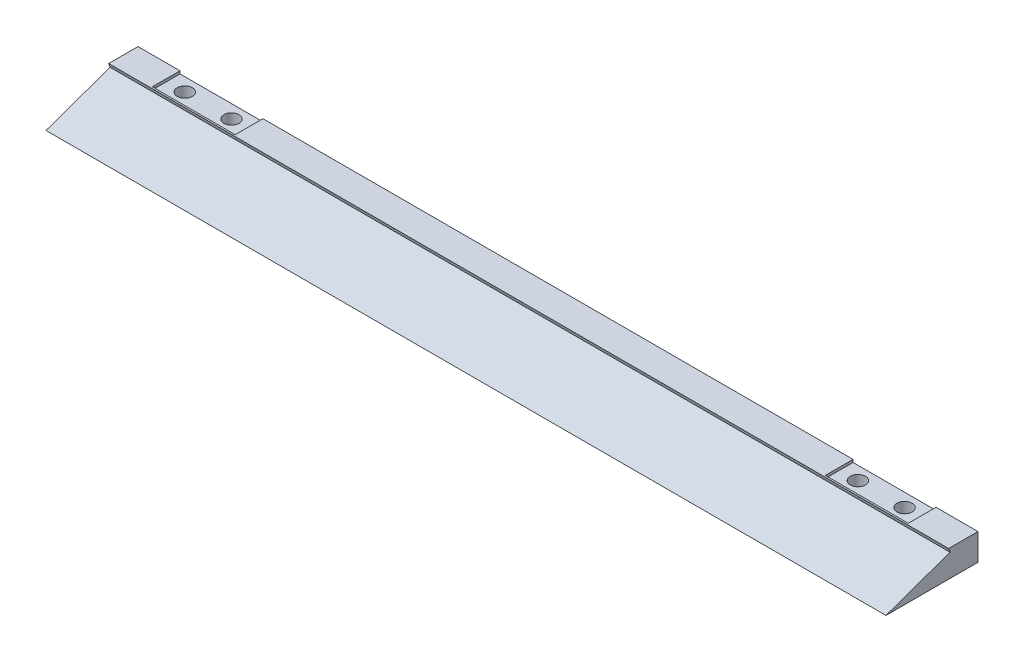
SolidWorks part; units mm, degrees
material "1023 Carbon Steel Sheet (SS)"
ref_plane "Front Plane" through (0, 0, 0) normal (0, 0, 1) x (1, 0, 0)
ref_plane "Top Plane" through (0, 0, 0) normal (0, 1, 0) x (1, 0, 0)
ref_plane "Right Plane" through (0, 0, 0) normal (1, 0, 0) x (0, 0, -1)
sketch "Sketch1" plane through (0, 0, 0) normal (0, 1, 0) x (1, 0, 0)
  line L1 (-100, -15) -> (100, -15)
  line L2 (-100, -15) -> (-100, 15)
  line L3 (-100, 15) -> (100, 15)
  line L4 (100, -15) -> (100, 15)
  line L5 (-100, -15) -> (100, 15) construction
  line L6 (-100, 15) -> (100, -15) construction
  point P0 (0, 0)
  dimension "D1" = 200
  dimension "D2" = 30
extrude "Base" add sketch "Sketch1" along normal blind 6.35
ref_plane "Midplane" through (0, 0, 0) normal (1, 0, 0) x (0, 0, -1)
sketch "Sketch2" plane through (100, 0, 0) normal (1, 0, 0) x (0, 0, -1)
  line L0 (-6.9075, 0) -> (11, 6.35)
  line L1 (-15, 0) -> (15, 0) construction
  line L2 (-15, 6.35) -> (15, 6.35) construction
  line L3 (11, 6.35) -> (11, 0)
  line L4 (11, 0) -> (-6.9075, 0)
  line L5 (15, 6.35) -> (15, 0) construction
  line L7 (11, 6.35) -> (-15, 6.35)
  line L8 (-15, 6.35) -> (-15, 0)
  line L9 (-15, 0) -> (-6.9075, 0)
  line L10 (8.3421, 5.4075) -> (8.0079, 6.35)
  line M3 (-15, 0) -> (15, 0)
  line M5 (15, 6.35) -> (-15, 6.35)
  line M6 (-15, 6.35) -> (-15, 0)
  dimension "D1" = 19
  dimension "D2" = 4
  dimension "D3" = 1
extrude "WedgeCut" cut sketch "Sketch2" against normal up to next contours L0 M3 M5 M6 region at (100, 3.7005, 5.8885)
sketch "Sketch3" plane through (0, 6.35, 0) normal (0, 1, 0) x (1, 0, 0)
  line L0 (-100, 15) -> (-100, 8.0079) construction
  line L1 (-90, 8.396) -> (-70.254, 8.396)
  line L2 (-90, 8.396) -> (-90, 15)
  line L3 (-90, 15) -> (-70.254, 15)
  line L4 (-70.254, 8.396) -> (-70.254, 15)
  line L5 (-90, 8.396) -> (-70.254, 15) construction
  line L6 (-90, 15) -> (-70.254, 8.396) construction
  line L7 (70.254, 15) -> (90, 15)
  line L8 (70.254, 15) -> (70.254, 8.396)
  line L9 (70.254, 8.396) -> (90, 8.396)
  line L10 (90, 15) -> (90, 8.396)
  line L11 (70.254, 15) -> (90, 8.396) construction
  line L12 (70.254, 8.396) -> (90, 15) construction
  line L13 (100, 15) -> (-100, 15) construction
  line L14 (100, 8.0079) -> (100, 15) construction
  point P0 (-80.127, 11.698)
  point P5 (80.127, 11.698)
  dimension "D1" = 6.604
  dimension "D2" = 19.746
  dimension "D3" = 10
  dimension "D4" = 19.746
  dimension "D5" = 10
  dimension "D6" = 6.604
extrude "Hinge Cutout" cut sketch "Sketch3" against normal blind 0.635
sketch "Sketch4" plane through (0, 5.715, 0) normal (0, 1, 0) x (1, 0, 0)
  line L0 (90, 15) -> (70.254, 15) construction
  circle A0 centre (74.5644, 11.825) radius 1.8034
  circle A1 centre (85.6896, 11.825) radius 1.8034
  point P6 (80.127, 15)
  dimension "D5" = 3.6068
  dimension "D6" = 3.6068
  dimension "D1" = 5.5626
  dimension "D2" = 5.5626
  dimension "D3" = 3.175
  dimension "D4" = 3.175
extrude "Hinge Hole Cut" cut sketch "Sketch4" against normal up to next
sketch "Sketch5" plane through (0, 0, 0) normal (0, -1, 0) x (1, 0, 0)
  line L1 (72.0394, -14.35) -> (77.0894, -14.35)
  line L2 (72.0394, -14.35) -> (72.0394, -9.3)
  line L3 (72.0394, -9.3) -> (77.0894, -9.3)
  line L4 (77.0894, -14.35) -> (77.0894, -9.3)
  line L5 (72.0394, -14.35) -> (77.0894, -9.3) construction
  line L6 (72.0394, -9.3) -> (77.0894, -14.35) construction
  line L7 (83.1646, -14.35) -> (88.2146, -14.35)
  line L8 (83.1646, -14.35) -> (83.1646, -9.3)
  line L9 (83.1646, -9.3) -> (88.2146, -9.3)
  line L10 (88.2146, -14.35) -> (88.2146, -9.3)
  line L11 (83.1646, -14.35) -> (88.2146, -9.3) construction
  line L12 (83.1646, -9.3) -> (88.2146, -14.35) construction
  point P0 (74.5644, -11.825)
  point P6 (85.6896, -11.825)
  dimension "D1" = 5.05
  dimension "D2" = 5.05
  dimension "D3" = 5.05
  dimension "D4" = 5.05
extrude "Hinge Nut Cut" cut sketch "Sketch5" against normal blind 2
mirror "Hinge Hole Mirror" about plane through (0, 0, 0) normal (1, 0, 0) of "Hinge Nut Cut", "Hinge Hole Cut"
sketch "Sketch6" plane through (0, 0, 0) normal (0, -1, 0) x (-1, 0, 0)
  circle A0 centre (-80, 5) radius 4.7625
  circle A1 centre (-40, 5) radius 4.7625
  circle A2 centre (0, 5) radius 4.7625
  circle A3 centre (40, 5) radius 4.7625
  circle A4 centre (80, 5) radius 4.7625
  dimension "D1" = 40
  dimension "D2" = 40
  dimension "D3" = 40
  dimension "D4" = 40
  dimension "D5" = 9.525
  dimension "D6" = 5
extrude "Cut-Extrude1" cut sketch "Sketch6" against normal blind 1.5875
